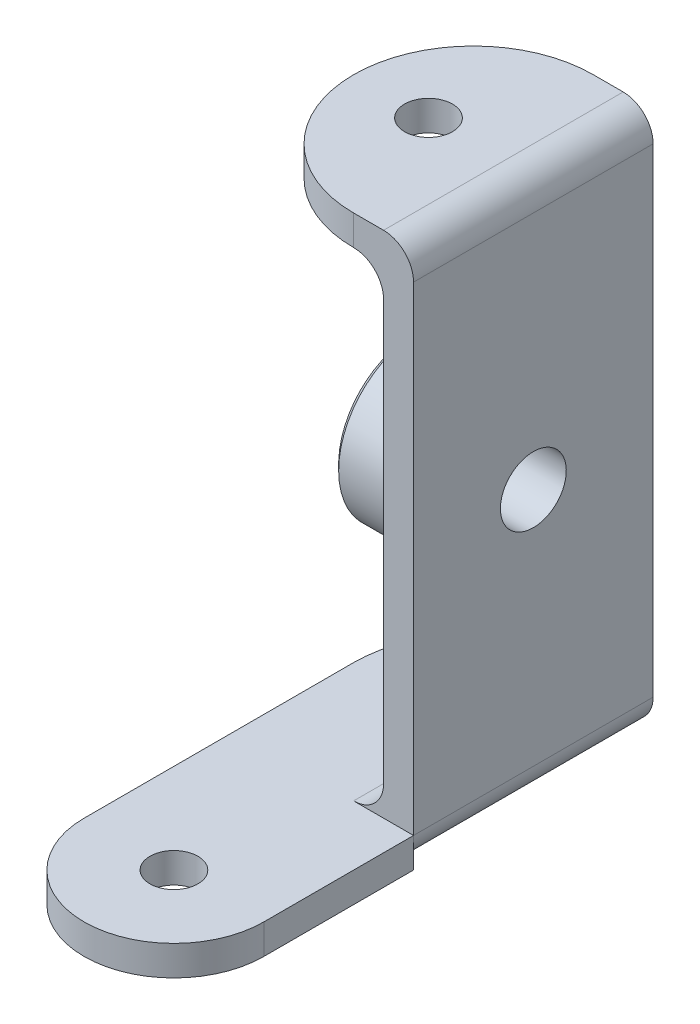
SolidWorks part; units mm, degrees
ref_plane "Front Plane" through (0, 0, 0) normal (0, 0, 1) x (1, 0, 0)
ref_plane "Top Plane" through (0, 0, 0) normal (0, 1, 0) x (1, 0, 0)
ref_plane "Right Plane" through (0, 0, 0) normal (1, 0, 0) x (0, 0, -1)
sketch "Sketch1" plane through (0, 0, 0) normal (0, 0, 1) x (1, 0, 0)
  line L0 (0, 45) -> (25, 45)
  line L1 (30, 40) -> (30, -40)
  line L2 (25, -45) -> (0, -45)
  line L3 (0, 40) -> (20, 40)
  line L4 (25, 35) -> (25, -35)
  line L5 (20, -40) -> (0, -40)
  line L6 (0, 45) -> (0, 40)
  line L7 (0, -40) -> (0, -45)
  line L8 (30, 45) -> (30, -45) construction
  line L9 (30, -45) -> (0, -45) construction
  line L10 (25, 40) -> (25, -40) construction
  line L11 (25, -40) -> (0, -40) construction
  line L12 (0, 45) -> (30, 45) construction
  line L13 (0, 40) -> (25, 40) construction
  arc A0 (30, -40) -> (25, -45) centre (25, -40) cw
  arc A1 (25, -35) -> (20, -40) centre (20, -35) cw
  arc A2 (25, 45) -> (30, 40) centre (25, 40) cw
  arc A3 (20, 40) -> (25, 35) centre (20, 35) cw
  point P2 (30, 0)
  point P13 (30, -45)
  dimension "D4" = 5
  dimension "D2" = 90
  dimension "D3" = 30
  dimension "D1" = 5
extrude "Boss-Extrude2" add sketch "Sketch1" along normal mid plane 40
sketch "Sketch2" plane through (25, 0, 0) normal (-1, 0, 0) x (0, 0, 1)
  circle A0 centre (0, 0) radius 13.5
  circle A1 centre (0, 0) radius 5.5
  dimension "D1" = 27
  dimension "D2" = 11
extrude "Boss-Extrude3" add sketch "Sketch2" along normal blind 15 contours A0 A1 | A1 region at (25, 0, -13.1182) region at (25, 0, 0)
extrude "Cut-Extrude1" cut sketch "Sketch2<3>" against normal through all both and the other way through all contours A1 region at (25, 0, 0)
sketch "Sketch2<3>" plane through (25, 0, 0) normal (-1, 0, 0) x (0, 0, 1) same geometry as "Sketch2"
chamfer "Chamfer1" distance 1 angle 45 1 edges at (10, -13.5, 0)
sketch "Sketch3" plane through (0, 45, 0) normal (0, 1, 0) x (1, 0, 0)
  line L0 (25, 20) -> (0, 20) construction
  circle A0 centre (12.5, 0) radius 4
  point P7 (12.5, 20)
  dimension "D1" = 8
extrude "Cut-Extrude2" cut sketch "Sketch3" against normal blind 10
fillet "Fillet2" 2 edges at (0, 42.5, 20) (0, 42.5, -20) type full round first side face at (17.0118, 0, 20) second side face at (17.0118, 0, -20) middle face at (0, 42.5, 0)
fillet "Fillet3" 2 edges at (0, -42.5, -20) (0, -42.5, 20) type full round first side face at (20.3766, -3.6364, -20) second side face at (20.3766, -3.6364, 20) middle face at (0, -42.5, 0)
sketch "Sketch4" plane through (0, -40, 0) normal (0, 1, 0) x (1, 0, 0)
  circle A1 centre (12.5, 0) radius 4
  circle A2 centre (12.5, 0) radius 4
  dimension "D1" = 0
extrude "Cut-Extrude3" cut sketch "Sketch4" against normal blind 10
sketch "Sketch6" plane through (0, 0, 20) normal (0, 0, 1) x (1, 0, 0)
  line L0 (0, -40) -> (0, -45) construction
  line L1 (20, -40) -> (0, -40) construction
  line L2 (0, -45) -> (20, -45) construction
  line L4 (0, -40) -> (0, -45)
  line L5 (20, -40) -> (0, -40)
  line L6 (0, -45) -> (30, -45)
  line L8 (20, -40) -> (30, -40)
  line L10 (30, -40) -> (30, -45)
extrude "Boss-Extrude4" add sketch "Sketch6" along normal blind 40 and the other way up to surface other way up to face at (10, -42.5, 0)
sketch "Sketch7" plane through (0, -40, 0) normal (0, 1, 0) x (1, 0, 0)
  line L0 (30, -60) -> (0, -60) construction
  circle A0 centre (15, -45) radius 4
  point P5 (15, -60)
  dimension "D1" = 8
  dimension "D2" = 15
extrude "Cut-Extrude4" cut sketch "Sketch7" against normal blind 30
fillet "Fillet5" 2 edges at (30, -42.5, 60) (0, -42.5, 60) type full round first side face at (30, -42.5, 40) second side face at (0, -42.5, 30) middle face at (15, -42.5, 60)
sketch "Sketch8" plane through (10, 0, 0) normal (-1, 0, 0) x (0, 0, 1)
  circle A0 centre (0, 0) radius 10
  dimension "D1" = 20
extrude "Cut-Extrude5" cut sketch "Sketch8" against normal blind 5
